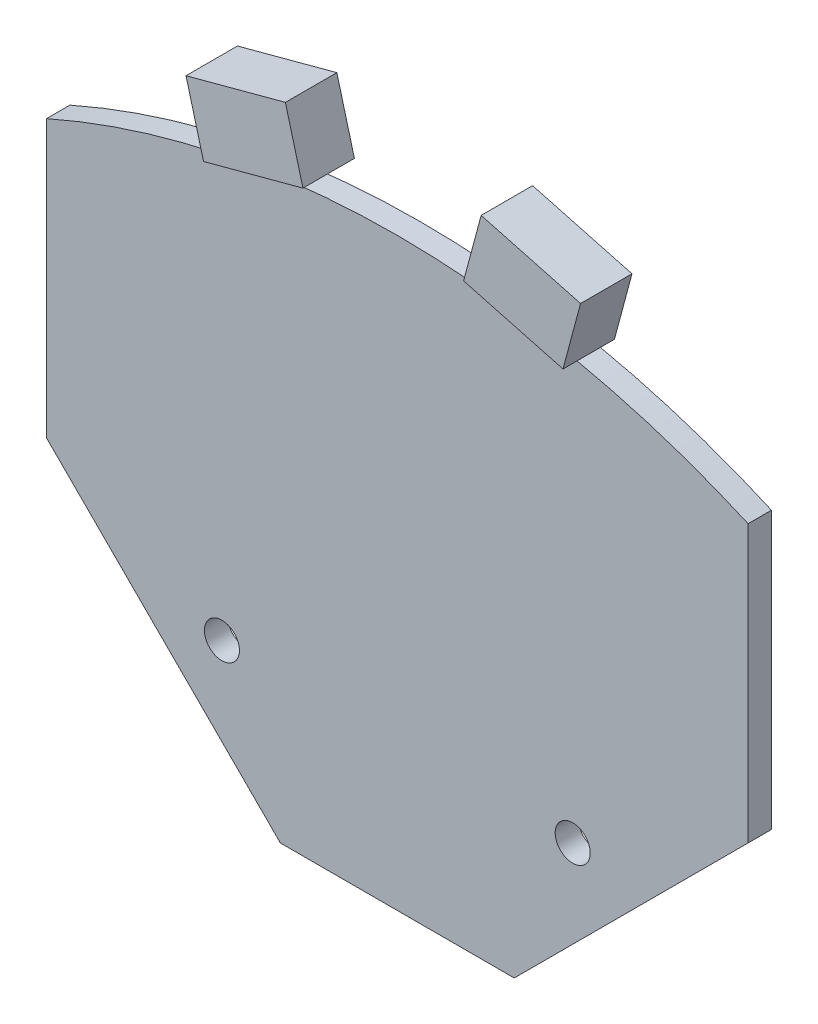
SolidWorks part; units mm, degrees
ref_plane "Plan de face" through (0, 0, 0) normal (0, 0, 1) x (1, 0, 0)
ref_plane "Plan de dessus" through (0, 0, 0) normal (0, 1, 0) x (1, 0, 0)
ref_plane "Plan de droite" through (0, 0, 0) normal (1, 0, 0) x (0, 0, -1)
sketch "Esquisse3" plane through (0, 0, 0) normal (0, 0, 1) x (1, 0, 0)
  line L0 (-221.8822, 0) -> (10872.2265, 0) construction
  line L1 (-20, 20) -> (0, 0)
  line L2 (1.63, 56.2664) -> (3.1312, 50.664)
  line L3 (-20, 43.6461) -> (-20, 20)
  line L4 (1.63, 56.2664) -> (-6.8701, 53.9888)
  line L5 (40, 43.6461) -> (40, 20)
  line L6 (3.1312, 50.664) -> (-5.369, 48.3864)
  line L7 (-6.8701, 53.9888) -> (-5.369, 48.3864)
  line L8 (0, 0) -> (20, 0)
  line L9 (25.369, 48.3864) -> (26.8701, 53.9888)
  line L10 (20, 0) -> (40, 20)
  line L11 (25.369, 48.3864) -> (16.8688, 50.664)
  line L12 (26.8701, 53.9888) -> (18.37, 56.2664)
  line L13 (16.8688, 50.664) -> (18.37, 56.2664)
  line L14 (10, -1000) -> (10, 49000) construction
  arc A0 (40, 43.6461) -> (-20, 43.6461) centre (10, -24) ccw
  circle A1 centre (25, 12.5) radius 1.5
  circle A2 centre (-5, 12.5) radius 1.5
  point P11 (10, 0)
  point P25 (0, 45)
  dimension "D4" = 148
  dimension "D9" = 3
  dimension "D1" = 20
  dimension "D2" = 60
  dimension "D3" = 15
  dimension "D5" = 24
  dimension "D6" = 5.8
  dimension "D7" = 8.8
  dimension "D8" = 15
  dimension "D10" = 12.5
  dimension "D11" = 15
  dimension "D12" = 10
  dimension "D13" = 45
  dimension "D15" = 8.37
extrude "Boss.-Extru.1" add sketch "Esquisse3" along normal blind 3.2 and the other way blind 1.2 contours L4 L7 L6 L2 | L12 L13 L11 L9 region at (-1.8695, 52.3264, 0)
extrude "Boss.-Extru.2" add sketch "Esquisse3<3>" along normal blind 2 separate body contours L5 A0 L3 L1 L8 L10 A1 A2 region at (10, 26.8796, 0)
sketch "Esquisse3<3>" plane through (0, 0, 0) normal (0, 0, 1) x (1, 0, 0) same geometry as "Esquisse3"
